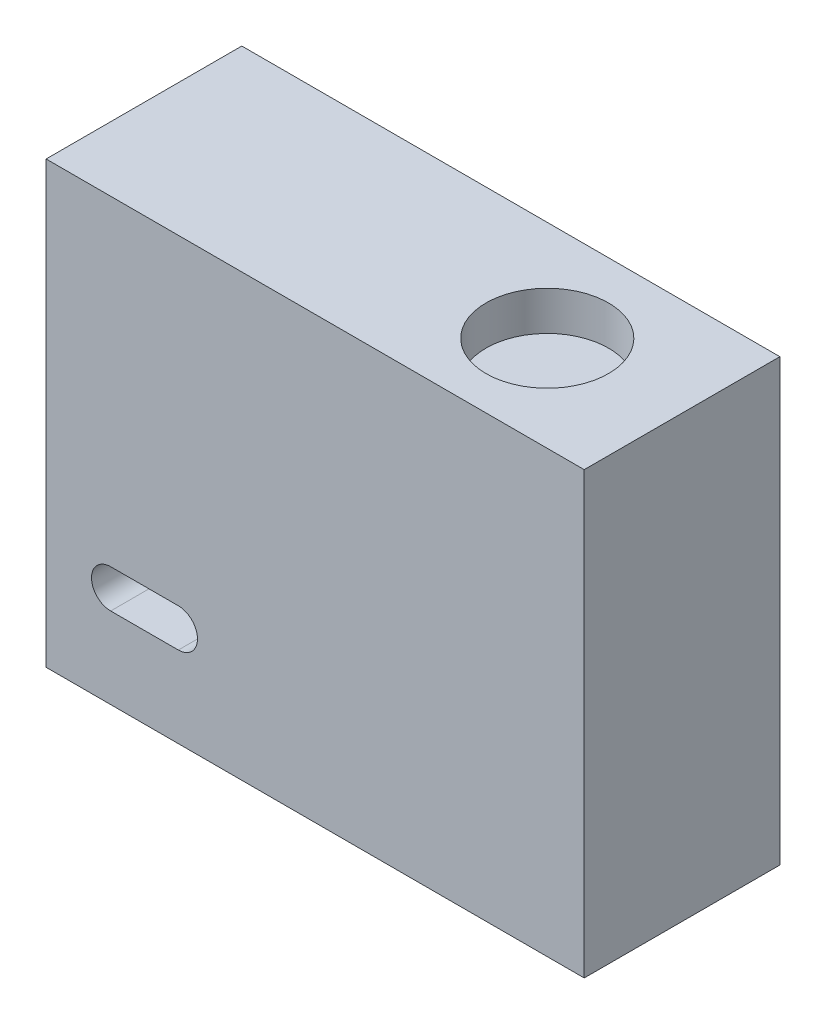
SolidWorks part; units mm, degrees
ref_plane "前视基准面" through (0, 0, 0) normal (0, 0, 1) x (1, 0, 0)
ref_plane "上视基准面" through (0, 0, 0) normal (0, 1, 0) x (1, 0, 0)
ref_plane "右视基准面" through (0, 0, 0) normal (1, 0, 0) x (0, 0, -1)
sketch "草图1" plane through (0, 0, 0) normal (0, 0, 1) x (1, 0, 0)
  line L1 (-55, 45) -> (55, 45)
  line L2 (-55, 45) -> (-55, -45)
  line L3 (-55, -45) -> (55, -45)
  line L4 (55, 45) -> (55, -45)
  line L5 (-55, 45) -> (55, -45) construction
  line L6 (-55, -45) -> (55, 45) construction
  point P0 (0, 0)
  dimension "D1" = 110
  dimension "D2" = 90
extrude "凸台-拉伸1" add sketch "草图1" along normal blind 40
sketch "草图2" plane through (0, 0, 0) normal (0, 0, 1) x (1, 0, 0)
  line L1 (-47.5, 30) -> (47.5, 30)
  line L2 (-47.5, 30) -> (-47.5, -30)
  line L3 (-47.5, -30) -> (47.5, -30)
  line L4 (47.5, 30) -> (47.5, -30)
  line L5 (-47.5, 30) -> (47.5, -30) construction
  line L6 (-47.5, -30) -> (47.5, 30) construction
  point P0 (0, 0)
  dimension "D1" = 95
  dimension "D2" = 60
extrude "切除-拉伸1" cut sketch "草图2" along normal blind 30
ref_plane "基准面4" through (0, 45, 0) normal (0, 1, 0) x (1, 0, 0)
sketch "草图3" plane through (0, 45, 0) normal (0, 1, 0) x (1, 0, 0)
  circle A0 centre (27.9639, -20.5145) radius 12.5207
  point P2 (27.9639, -20.5145)
extrude "切除-拉伸2" cut sketch "草图3" against normal blind 8
ref_plane "基准面5" through (0, 0, 40) normal (0, 0, 1) x (1, 0, 0)
sketch "草图4" plane through (0, 0, 40) normal (0, 0, 1) x (1, 0, 0)
  line L0 (-41.8014, -24.5049) -> (-27.9732, -24.5049) construction
  line L1 (-41.8014, -20.5872) -> (-27.9732, -20.5872)
  line L2 (-41.8014, -28.4225) -> (-27.9732, -28.4225)
  arc A0 (-41.8014, -20.5872) -> (-41.8014, -28.4225) centre (-41.8014, -24.5049) ccw
  arc A1 (-27.9732, -28.4225) -> (-27.9732, -20.5872) centre (-27.9732, -24.5049) ccw
  point P2 (-34.8873, -24.5049)
  point P7 (-35.1208, -27.3078)
  point P8 (0, 0)
extrude "切除-拉伸3" cut sketch "草图4" against normal blind 18
